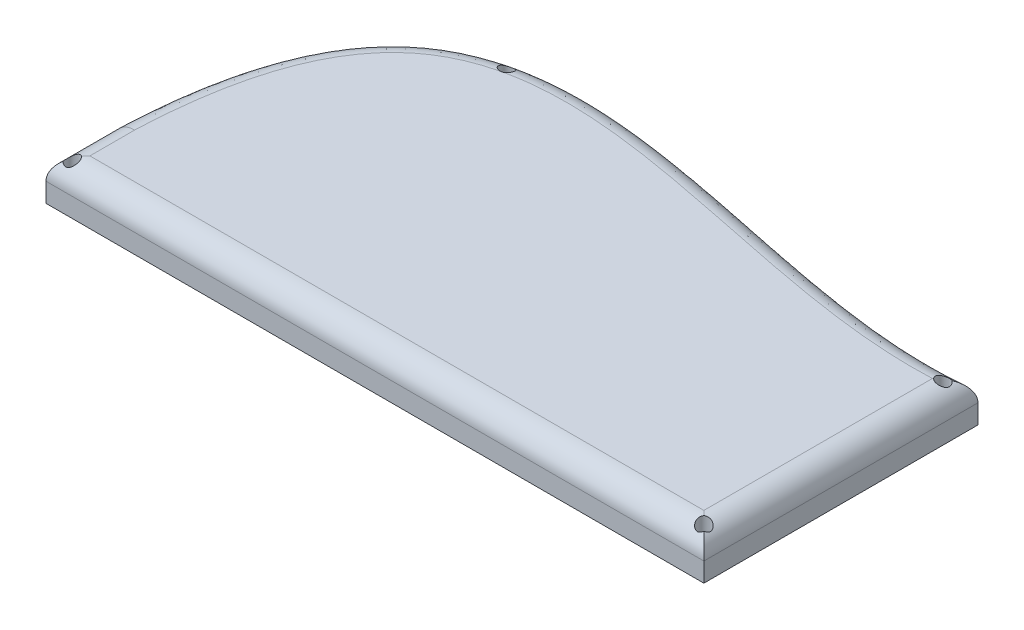
SolidWorks part; units mm, degrees
ref_plane "Front Plane" through (0, 0, 0) normal (0, 0, 1) x (1, 0, 0)
ref_plane "Top Plane" through (0, 0, 0) normal (0, 1, 0) x (1, 0, 0)
ref_plane "Right Plane" through (0, 0, 0) normal (1, 0, 0) x (0, 0, -1)
sketch "Sketch1" plane through (0, 0, 0) normal (0, 1, 0) x (1, 0, 0)
  line L1 (0, 0) -> (76.2, 0)
  line L2 (0, 0) -> (0, 38.1)
  line L3 (0, 38.1) -> (76.2, 38.1)
  line L4 (76.2, 0) -> (76.2, 38.1)
  spline S0 degree 3 poles (0, 0) (-2.1647, 62.6103) (45.4594, 28.2973) (76.2, 31.75) knots 0 0 0 0 1 1 1 1
  dimension "D7" = 104.394
  dimension "D1" = 76.2
  dimension "D2" = 38.1
  dimension "D3" = 31.75
  dimension "D4" = 19.304
  dimension "D5" = 33.02
  dimension "D6" = 18.796
extrude "Boss-Extrude1" add sketch "Sketch1" along normal blind 4.7625 contours S0 L2 L1 L4 region at (38.2, 0, -17.2224)
fillet "Fillet1" radius 2.54 4 edges at (0, 4.7625, -3.8856) (38.1, 4.7625, 0) (76.2, 4.7625, -15.875) type face fillet first side face at (28.575, 4.7625, -6.8829) second side face at (76.2, 2.3812, -15.875) second side face at (0, 2.3812, -3.8856) second side face at (19.05, 2.3812, -13.7659) second side face at (38.1, 2.3812, 0)
sketch "Sketch2" plane through (0, 0, 0) normal (0, -1, 0) x (1, 0, 0)
  line L0 (0, 0) -> (76.2, 0) construction
  line L1 (0, 0) -> (0, -7.7712) construction
  line L2 (76.2, 0) -> (76.2, -31.75) construction
  circle A0 centre (74.295, -29.591) radius 0.762
  circle A1 centre (74.676, -1.524) radius 0.762
  circle A2 centre (1.524, -1.524) radius 0.762
  circle A3 centre (17.78, -35.56) radius 0.762
  dimension "D9" = 1.524
  dimension "D1" = 1.524
  dimension "D2" = 1.524
  dimension "D3" = 1.524
  dimension "D4" = 1.524
  dimension "D5" = 1.905
  dimension "D6" = 2.159
  dimension "D7" = 17.78
  dimension "D8" = 35.56
extrude "Cut-Extrude1" cut sketch "Sketch2" against normal through all
